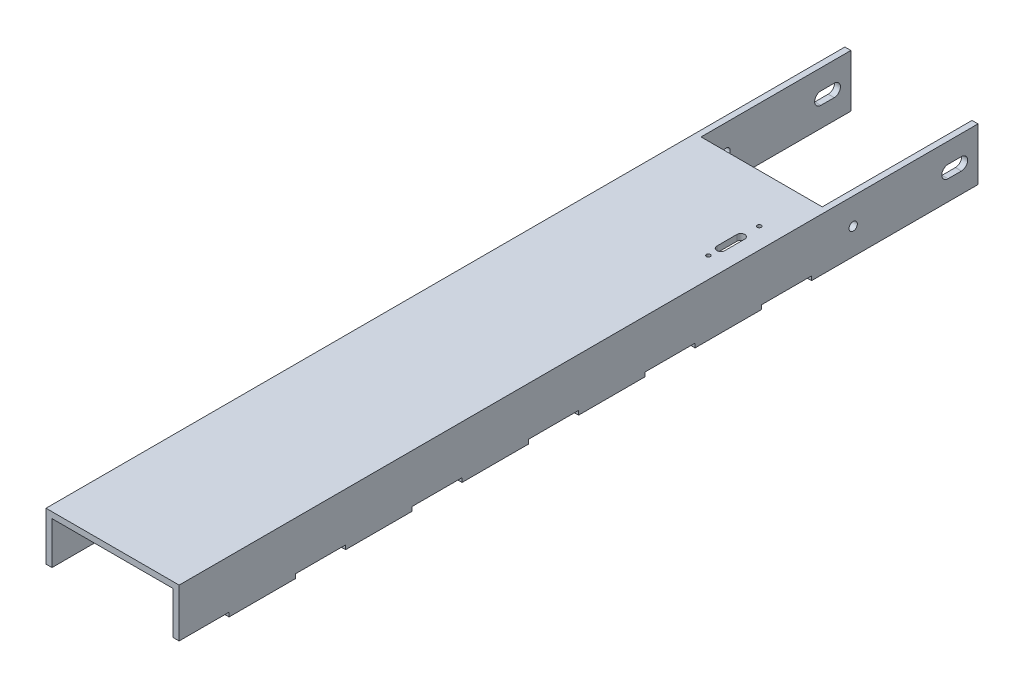
SolidWorks part; units mm, degrees
ref_plane "Front Plane" through (0, 0, 0) normal (0, 0, 1) x (1, 0, 0)
ref_plane "Top Plane" through (0, 0, 0) normal (0, 1, 0) x (1, 0, 0)
ref_plane "Right Plane" through (0, 0, 0) normal (1, 0, 0) x (0, 0, -1)
sketch "Sketch1" plane through (0, 0, 0) normal (0, 0, 1) x (1, 0, 0)
  line L0 (-50.8, 0) -> (50.8, 0)
  line L1 (50.8, 0) -> (50.8, -40.132)
  line L2 (50.8, -40.132) -> (46.228, -40.132)
  line L3 (46.228, -40.132) -> (46.228, -4.572)
  line L4 (46.228, -4.572) -> (-46.228, -4.572)
  line L5 (-46.228, -4.572) -> (-46.228, -40.132)
  line L6 (-46.228, -40.132) -> (-50.8, -40.132)
  line L7 (-50.8, -40.132) -> (-50.8, 0)
  point P8 (0, 0)
  dimension "D1" = 40.132
  dimension "D2" = 4.572
  dimension "D3" = 4.572
  dimension "D4" = 101.6
extrude "Boss-Extrude1" add sketch "Sketch1" along normal blind 609.6
sketch "Sketch3" plane through (0, 0, 0) normal (0, 1, 0) x (1, 0, 0)
  line L0 (50.8, 0) -> (-50.8, 0) construction
  line L1 (-46.228, -114.3) -> (46.228, -114.3)
  line L2 (-46.228, -114.3) -> (-46.228, 0)
  line L3 (-46.228, 0) -> (46.228, 0)
  line L4 (46.228, -114.3) -> (46.228, 0)
  line L5 (-46.228, -114.3) -> (46.228, 0) construction
  line L6 (-46.228, 0) -> (46.228, -114.3) construction
  line L7 (-46.228, -609.6) -> (-46.228, 0) construction
  line L8 (46.228, -609.6) -> (46.228, 0) construction
  line L9 (34.925, -165.1) -> (34.925, -180.34) construction
  line L10 (37.973, -165.1) -> (37.973, -180.34)
  line L11 (31.877, -165.1) -> (31.877, -180.34)
  arc A0 (37.973, -165.1) -> (31.877, -165.1) centre (34.925, -165.1) ccw
  arc A1 (31.877, -180.34) -> (37.973, -180.34) centre (34.925, -180.34) ccw
  circle A2 centre (34.925, -151.13) radius 1.524
  circle A3 centre (34.925, -189.865) radius 1.524
  point P0 (0, -57.15)
  point P13 (34.925, -172.72)
  dimension "D2" = 6.096
  dimension "D6" = 3.048
  dimension "D1" = 114.3
  dimension "D3" = 15.24
  dimension "D4" = 50.8
  dimension "D5" = 8.255
  dimension "D7" = 13.97
  dimension "D8" = 9.525
extrude "Cut-Extrude1" cut sketch "Sketch3" against normal through all
sketch "Sketch4" plane through (50.8, 0, 0) normal (1, 0, 0) x (0, 0, -1)
  line L0 (-12.7, -20.066) -> (-22.86, -20.066) construction
  line L1 (-12.7, -24.8285) -> (-22.86, -24.8285)
  line L2 (-12.7, -15.3035) -> (-22.86, -15.3035)
  line L3 (0, -40.132) -> (0, 0) construction
  line L4 (-520.7, -40.132) -> (-482.6, -40.132)
  line L5 (-609.6, -40.132) -> (-571.5, -40.132)
  line L6 (-609.6, -40.132) -> (-609.6, -36.957)
  line L7 (-609.6, -36.957) -> (-571.5, -36.957)
  line L8 (-571.5, -40.132) -> (-571.5, -36.957)
  line L9 (-520.7, -40.132) -> (-520.7, -36.957)
  line L10 (-520.7, -36.957) -> (-482.6, -36.957)
  line L11 (-482.6, -40.132) -> (-482.6, -36.957)
  line L12 (-431.8, -40.132) -> (-393.7, -40.132)
  line L13 (-431.8, -40.132) -> (-431.8, -36.957)
  line L14 (-431.8, -36.957) -> (-393.7, -36.957)
  line L15 (-393.7, -40.132) -> (-393.7, -36.957)
  line L16 (-342.9, -40.132) -> (-304.8, -40.132)
  line L17 (-342.9, -40.132) -> (-342.9, -36.957)
  line L18 (-342.9, -36.957) -> (-304.8, -36.957)
  line L19 (-304.8, -40.132) -> (-304.8, -36.957)
  line L20 (-254, -40.132) -> (-215.9, -40.132)
  line L21 (-254, -40.132) -> (-254, -36.957)
  line L22 (-254, -36.957) -> (-215.9, -36.957)
  line L23 (-215.9, -40.132) -> (-215.9, -36.957)
  line L24 (-165.1, -40.132) -> (-127, -40.132)
  line L25 (-165.1, -40.132) -> (-165.1, -36.957)
  line L26 (-165.1, -36.957) -> (-127, -36.957)
  line L27 (-127, -40.132) -> (-127, -36.957)
  arc A0 (-12.7, -24.8285) -> (-12.7, -15.3035) centre (-12.7, -20.066) ccw
  arc A1 (-22.86, -15.3035) -> (-22.86, -24.8285) centre (-22.86, -20.066) ccw
  circle A2 centre (-95.25, -20.066) radius 3.175
  point P3 (-17.78, -20.066)
  point P10 (0, -20.066)
  dimension "D3" = 9.525
  dimension "D5" = 6.35
  dimension "D1" = 10.16
  dimension "D2" = 12.7
  dimension "D4" = 95.25
  dimension "D6" = 3.175
  dimension "D7" = 38.1
  dimension "D8" = 6
extrude "Cut-Extrude2" cut sketch "Sketch4" against normal through all
